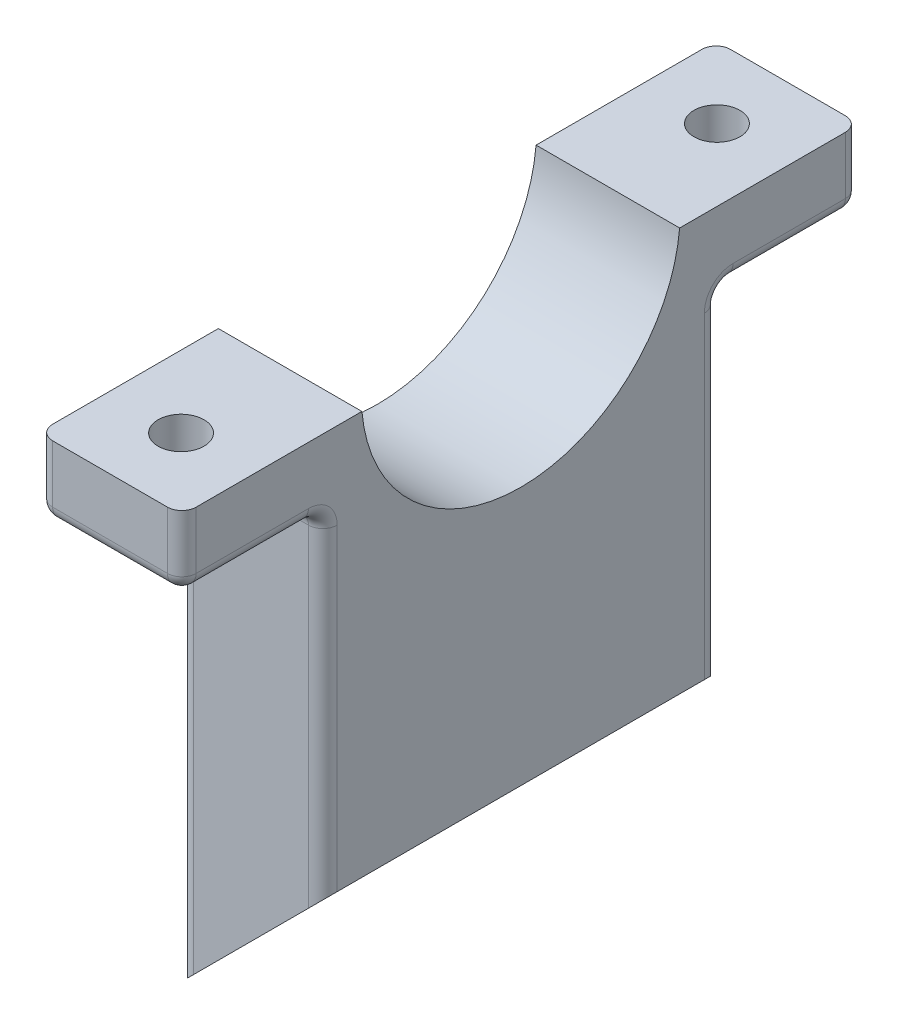
SolidWorks part; units mm, degrees
ref_plane "Front Plane" through (0, 0, 0) normal (0, 0, 1) x (1, 0, 0)
ref_plane "Top Plane" through (0, 0, 0) normal (0, 1, 0) x (1, 0, 0)
ref_plane "Right Plane" through (0, 0, 0) normal (1, 0, 0) x (0, 0, -1)
sketch "Sketch4" plane through (0, 0, 0) normal (1, 0, 0) x (0, 0, -1)
  line L2 (-23.6125, -1) -> (-23.6125, -6)
  line L3 (-23.6125, -6) -> (-13.7899, -6)
  line L4 (23.6125, -1) -> (23.6125, -6)
  line L5 (13.7899, -6) -> (23.6125, -6)
  line L7 (-23.6125, -1) -> (-11.0674, -1)
  line L8 (11.0674, -1) -> (23.6125, -1)
  line L10 (-13.7899, -6) -> (-13.7899, -39.1125)
  line L11 (13.7899, -6) -> (13.7899, -39.1125)
  line L12 (-13.7899, -39.1125) -> (13.7899, -39.1125)
  arc A0 (-11.0674, -1) -> (11.0674, -1) centre (0, 0) ccw
  point P3 (0, -11.1125)
  dimension "D2" = 22.225
  dimension "D1" = 5
  dimension "D3" = 22.1348
  dimension "D4" = 28
  dimension "D5" = 12.5451
  dimension "D6" = 12.5451
  dimension "D7" = 9.8226
  dimension "D8" = 9.8226
  dimension "D9" = 27.5799
extrude "Clamp Extrude" add sketch "Sketch4" along normal blind 10
sketch "Hole" plane through (0, -6, 0) normal (0, -1, 0) x (1, 0, 0)
  line L0 (0, 0) -> (10, 0)
  line L4 (0, 23.6125) -> (0, 13.7899) construction
  line L5 (10, 23.6125) -> (10, 13.7899) construction
  line L9 (8.3198, 18.6649) -> (6.6599, 21.5399)
  line L10 (10, 23.6125) -> (0, 23.6125) construction
  line L11 (10, 13.7899) -> (0, 13.7899) construction
  line L12 (6.6599, 21.5399) -> (3.3401, 21.5399)
  line L13 (3.3401, 21.5399) -> (1.6802, 18.6649)
  line L14 (1.6802, 18.6649) -> (3.3401, 15.7899)
  line L15 (3.3401, 15.7899) -> (6.6599, 15.7899)
  line L16 (6.6599, 15.7899) -> (8.3198, 18.6649)
  line L17 (10, 13.7899) -> (10, -13.7899) construction
  line L18 (6.6599, -15.7899) -> (8.3198, -18.6649)
  line L19 (3.3401, -15.7899) -> (6.6599, -15.7899)
  line L20 (1.6802, -18.6649) -> (3.3401, -15.7899)
  line L21 (3.3401, -21.5399) -> (1.6802, -18.6649)
  line L22 (6.6599, -21.5399) -> (3.3401, -21.5399)
  line L23 (8.3198, -18.6649) -> (6.6599, -21.5399)
  circle A0 centre (5, 18.6649) radius 1.6
  circle A3 centre (5, 18.6649) radius 2.875 construction
  circle A4 centre (5, -18.6649) radius 1.6
  dimension "D1" = 3.2
  dimension "D6" = 5.75
  dimension "D4" = 10
  dimension "D5" = 5
  dimension "D2" = 9.8226
  dimension "D3" = 4.875
sketch "Sketch10" plane through (0, 0, -13.7899) normal (0, 0, -1) x (-1, 0, 0)
  line L0 (0, -39.1125) -> (-10, -29.1125)
  line L1 (-10, -39.1125) -> (-10, -6) construction
  line L2 (-10, -29.1125) -> (-10, -39.1125)
  line L3 (-10, -39.1125) -> (0, -39.1125)
  dimension "D1" = 45
extrude "Cut-Extrude3" cut sketch "Sketch10" against normal through all
fillet "Fillet2" radius 1 12 edges at (10, -17.5562, 13.7899) (0, -6, 18.7012) (0, -6, -18.7012) (10, -6, 18.7012) (5, -6, 23.6125) (5, -6, 13.7899) (5, -6, -23.6125) (5, -6, -13.7899) (10, -6, -18.7012) (0, -22.5562, 13.7899) (0, -22.5562, -13.7899) (10, -17.5562, -13.7899)
fillet "Fillet3" radius 1 8 edges at (0.2929, -5.7071, -23.3196) (9.7071, -5.7071, -23.3196) (9.7071, -5.7071, 23.3196) (0.2929, -5.7071, 23.3196) (0, -3, -23.6125) (10, -3, -23.6125) (10, -3, 23.6125) (0, -3, 23.6125)
extrude "Cut-Extrude4" cut sketch "Hole" against normal blind 2.2 contours L14 L15 L16 L9 L12 L13 | L21 L20 L19 L18 L23 L22
extrude "Cut-Extrude5" cut sketch "Hole<5>" against normal through all contours A0 | A4
sketch "Hole<5>" plane through (0, -6, 0) normal (0, -1, 0) x (1, 0, 0) same geometry as "Hole"
equation "\"D5@Hole\"=\"D4@Hole\"/2"
equation "\"D3@Hole\"=\"D6@Hole\"/2+2"
equation "\"D6@Sketch4\"=\"D5@Sketch4\""
equation "\"D8@Sketch4\"=\"D7@Sketch4\""
